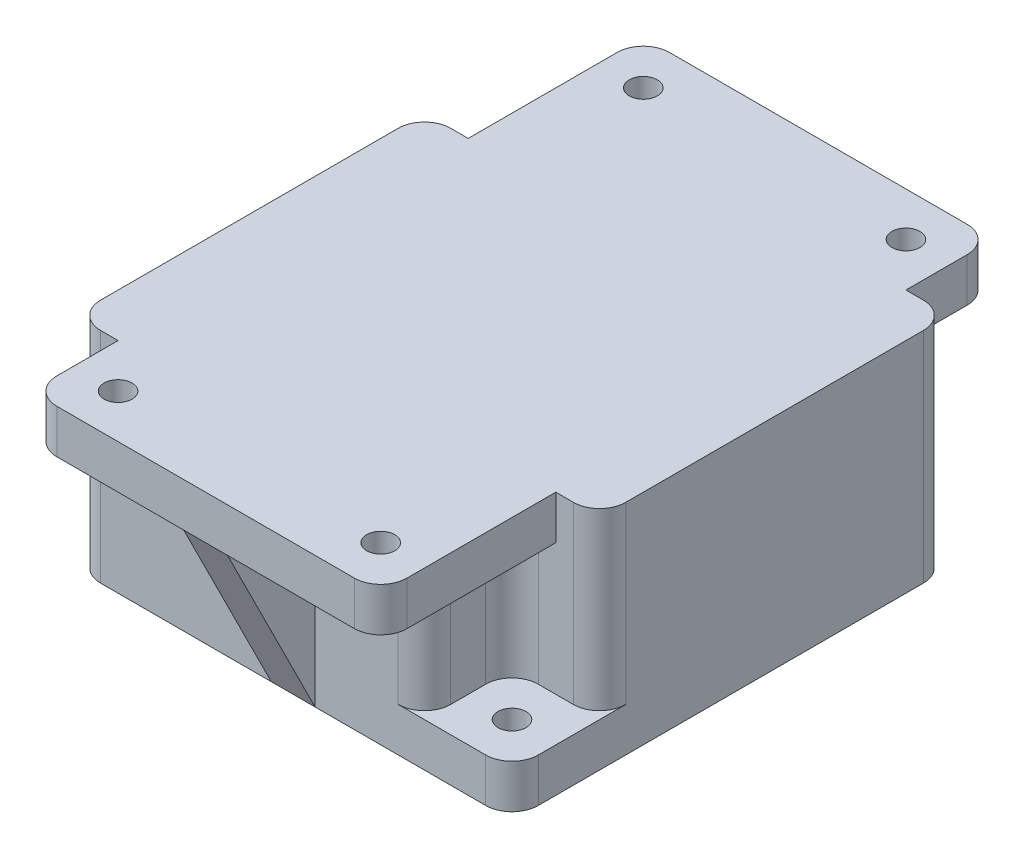
SolidWorks part; units mm, degrees
ref_plane "Plan de face" through (0, 0, 0) normal (0, 0, 1) x (1, 0, 0)
ref_plane "Plan de dessus" through (0, 0, 0) normal (0, 1, 0) x (1, 0, 0)
ref_plane "Plan de droite" through (0, 0, 0) normal (1, 0, 0) x (0, 0, -1)
sketch "Esquisse1" plane through (0, 0, 0) normal (0, 1, 0) x (1, 0, 0)
  line L0 (-20, 20) -> (20, 20) construction
  line L1 (-25, -25) -> (25, -25)
  line L2 (-25, -25) -> (-25, 25)
  line L3 (-25, 25) -> (25, 25)
  line L4 (25, -25) -> (25, 25)
  line L5 (-25, -25) -> (25, 25) construction
  line L6 (-25, 25) -> (25, -25) construction
  circle A0 centre (-20, 20) radius 1.6
  circle A1 centre (20, -20) radius 1.6
  point P0 (0, 0)
  point P10 (0, 0)
  dimension "D2" = 40
  dimension "D4" = 3.2
  dimension "D1" = 50
  dimension "D3" = 40
extrude "Boss.-Extru.1" add sketch "Esquisse1" along normal blind 25
fillet "Congé1" radius 3 4 edges at (-25, 12.5, -25) (-25, 12.5, 25) (25, 12.5, -25) (25, 12.5, 25)
sketch "Esquisse2" plane through (0, 25, 0) normal (0, 1, 0) x (1, 0, 0)
  line L0 (22, 25) -> (-22, 25) construction
  line L1 (-15, 15) -> (-25, 15)
  line L2 (-15, 15) -> (-15, 25)
  line L3 (-15, 25) -> (-25, 25)
  line L4 (-25, 15) -> (-25, 25)
  line L5 (-15, 15) -> (-25, 25) construction
  line L6 (-15, 25) -> (-25, 15) construction
  line L8 (15, -15) -> (25, -15)
  line L9 (15, -15) -> (15, -25)
  line L10 (15, -25) -> (25, -25)
  line L11 (25, -15) -> (25, -25)
  line L12 (15, -15) -> (25, -25) construction
  line L13 (15, -25) -> (25, -15) construction
  point P0 (-20, 20)
  point P9 (20, -20)
extrude "Enlèv. mat.-Extru.1" cut sketch "Esquisse2" against normal blind 20
fillet "Congé2" [suppressed] radius 3
sketch "Esquisse3" [suppressed] plane through (0, 42.5, 0) normal (0, -1, 0) x (1, 0, 0)
  line L0 (24.1213, 24.1213) -> (15.8787, 15.8787) construction
  line L1 (22.6536, 22.6536) -> (19.0287, 23.6249)
  line L2 (19.0287, 23.6249) -> (16.3751, 20.9713)
  line L3 (16.3751, 20.9713) -> (17.3464, 17.3464)
  line L4 (17.3464, 17.3464) -> (20.9713, 16.3751)
  line L5 (20.9713, 16.3751) -> (23.6249, 19.0287)
  line L6 (23.6249, 19.0287) -> (22.6536, 22.6536)
  line L7 (-15.8787, -15.8787) -> (-24.1213, -24.1213) construction
  line L9 (-22.6536, -22.6536) -> (-19.0287, -23.6249)
  line L10 (-19.0287, -23.6249) -> (-16.3751, -20.9713)
  line L11 (-16.3751, -20.9713) -> (-17.3464, -17.3464)
  line L12 (-17.3464, -17.3464) -> (-20.9713, -16.3751)
  line L13 (-20.9713, -16.3751) -> (-23.6249, -19.0287)
  line L14 (-23.6249, -19.0287) -> (-22.6536, -22.6536)
  circle A0 centre (20, 20) radius 3.25 construction
  arc A1 (25, 22) -> (22, 25) centre (22, 22) ccw construction
  arc A2 (15, 18) -> (18, 15) centre (18, 18) ccw construction
  arc A3 (-15, -18) -> (-18, -15) centre (-18, -18) ccw construction
  arc A4 (-25, -22) -> (-22, -25) centre (-22, -22) ccw construction
  circle A5 centre (-20, -20) radius 3.25 construction
  dimension "D1" = 6.5
  dimension "D2" = 6.5
extrude "Enlèv. mat.-Extru.2" [suppressed] cut sketch "Esquisse3" against normal blind 2.5
sketch "Esquisse4" plane through (0, 25, 0) normal (0, 1, 0) x (1, 0, 0)
  line L1 (-15, -30) -> (15, -30) construction
  line L2 (-15, -30) -> (-15, 30) construction
  line L3 (-15, 30) -> (15, 30) construction
  line L4 (15, -30) -> (15, 30) construction
  line L5 (-15, -30) -> (15, 30) construction
  line L6 (-15, 30) -> (15, -30) construction
  line L7 (20, -35) -> (-20, -35)
  line L8 (20, -35) -> (20, 35)
  line L9 (20, 35) -> (-20, 35)
  line L10 (-20, -35) -> (-20, 35)
  line L11 (20, -35) -> (-20, 35) construction
  line L12 (20, 35) -> (-20, -35) construction
  circle A0 centre (-15, 30) radius 1.6
  circle A1 centre (15, 30) radius 1.6
  circle A2 centre (15, -30) radius 1.6
  circle A3 centre (-15, -30) radius 1.6
  point P0 (0, 0)
  point P10 (0, 0)
  dimension "D1" = 3.2
  dimension "D2" = 30
  dimension "D3" = 60
  dimension "D4" = 5
  dimension "D5" = 5
extrude "Boss.-Extru.2" add sketch "Esquisse4" against normal blind 5
fillet "Congé3" radius 3 4 edges at (20, 22.5, 35) (-20, 22.5, 35) (20, 22.5, -35) (-20, 22.5, -35)
fillet "Congé4" radius 3 6 edges at (-25, 15, -15) (-15, 12.5, -25) (-15, 12.5, -15) (15, 12.5, 25) (15, 12.5, 15) (25, 15, 15)
fillet "Congé5" [suppressed] radius 3
sketch "Esquisse5" plane through (0, 20, 0) normal (0, -1, 0) x (1, 0, 0)
  line L1 (-15, -30) -> (15, -30) construction
  line L2 (-15, -30) -> (-15, 30) construction
  line L3 (-15, 30) -> (15, 30) construction
  line L4 (15, -30) -> (15, 30) construction
  line L5 (-15, -30) -> (15, 30) construction
  line L6 (-15, 30) -> (15, -30) construction
  line L7 (-13.3217, 26.6434) -> (-11.254, 29.7752)
  line L8 (-11.254, 29.7752) -> (-12.9323, 33.1317)
  line L9 (-12.9323, 33.1317) -> (-16.6783, 33.3566)
  line L10 (-16.6783, 33.3566) -> (-18.746, 30.2248)
  line L11 (-18.746, 30.2248) -> (-17.0677, 26.8683)
  line L12 (-17.0677, 26.8683) -> (-13.3217, 26.6434)
  line L13 (13.296, 26.592) -> (17.0994, 26.8203)
  line L14 (17.0994, 26.8203) -> (18.8034, 30.2283)
  line L15 (18.8034, 30.2283) -> (16.704, 33.408)
  line L16 (16.704, 33.408) -> (12.9006, 33.1797)
  line L17 (12.9006, 33.1797) -> (11.1966, 29.7717)
  line L18 (11.1966, 29.7717) -> (13.296, 26.592)
  line L19 (13.296, -26.592) -> (11.1966, -29.7717)
  line L20 (11.1966, -29.7717) -> (12.9006, -33.1797)
  line L21 (12.9006, -33.1797) -> (16.704, -33.408)
  line L22 (16.704, -33.408) -> (18.8034, -30.2283)
  line L23 (18.8034, -30.2283) -> (17.0994, -26.8203)
  line L24 (17.0994, -26.8203) -> (13.296, -26.592)
  line L25 (-13.296, -26.592) -> (-17.0994, -26.8203)
  line L26 (-17.0994, -26.8203) -> (-18.8034, -30.2283)
  line L27 (-18.8034, -30.2283) -> (-16.704, -33.408)
  line L28 (-16.704, -33.408) -> (-12.9006, -33.1797)
  line L29 (-12.9006, -33.1797) -> (-11.1966, -29.7717)
  line L30 (-11.1966, -29.7717) -> (-13.296, -26.592)
  circle A0 centre (-15, 30) radius 3.25 construction
  circle A1 centre (15, 30) radius 3.2998 construction
  circle A2 centre (15, -30) radius 3.2998 construction
  circle A3 centre (-15, -30) radius 3.2998 construction
  point P0 (0, 0)
  dimension "D1" = 6.5
extrude "Enlèv. mat.-Extru.3" cut sketch "Esquisse5" against normal blind 2.5
sketch "Esquisse6" plane through (0, 0, 0) normal (1, 0, 0) x (0, 0, -1)
  line L0 (-35, 20) -> (-25, 0)
  line L1 (-25, 0) -> (-25, 20)
  line L2 (-25, 20) -> (-35, 20)
  line L3 (35, 20) -> (25, 0)
  line L4 (25, 0) -> (25, 20)
  line L5 (25, 20) -> (35, 20)
extrude "Boss.-Extru.3" add sketch "Esquisse6" along normal blind 2.5 and the other way blind 2.5
